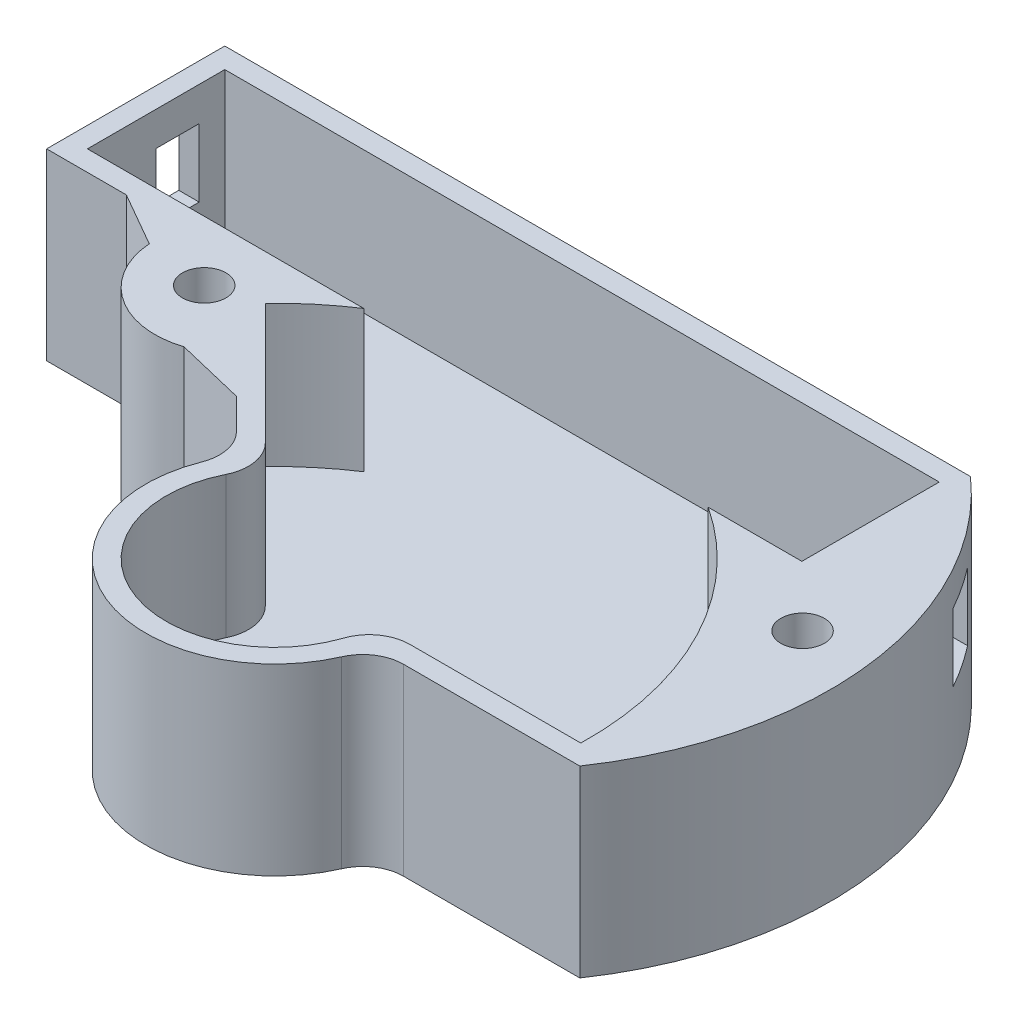
SolidWorks part; units mm, degrees
ref_plane "Alzado" through (0, 0, 0) normal (0, 0, 1) x (1, 0, 0)
ref_plane "Planta" through (0, 0, 0) normal (0, 1, 0) x (1, 0, 0)
ref_plane "Vista lateral" through (0, 0, 0) normal (1, 0, 0) x (0, 0, -1)
sketch "Croquis1" plane through (0, 0, 0) normal (0, 1, 0) x (1, 0, 0)
  line L0 (-35, 32.5) -> (35, -32.5) construction
  line L1 (-35, 32.5) -> (35, 32.5)
  line L2 (-35, 32.5) -> (-35, -32.5)
  line L3 (-35, -32.5) -> (35, -32.5)
  line L4 (35, 32.5) -> (35, -32.5)
  dimension "D1" = 70
  dimension "D2" = 65
extrude "Extruir1" add sketch "Croquis1" along normal blind 3.5
sketch "Croquis2" plane through (0, 3.5, 0) normal (0, 1, 0) x (1, 0, 0)
  line L0 (0, 32.5) -> (0, -32.5) construction
  line L1 (35, 32.5) -> (-35, 32.5) construction
  line L2 (-35, -32.5) -> (35, -32.5) construction
  circle A0 centre (0, -17.5) radius 3.1
  dimension "D1" = 6.2
  dimension "D2" = 15
extrude "Extruir2" cut sketch "Croquis2" against normal blind 5
sketch "Croquis3" plane through (0, 3.5, 0) normal (0, 1, 0) x (1, 0, 0)
  line L0 (0, -32.5) -> (0, 32.5) construction
  line L1 (-35, -32.5) -> (35, -32.5) construction
  line L2 (35, 32.5) -> (-35, 32.5) construction
  line L3 (-32.9868, -32.5) -> (-32.9868, 32.5) construction
  line L4 (-32.9868, 1.7) -> (-12.6633, 1.7)
  line L5 (18.8496, -32.5) -> (18.8496, 32.5) construction
  line L6 (-32.9868, 3.5) -> (18.8496, 3.5) construction
  line L7 (-32.9868, 2) -> (0, 2) construction
  line L8 (-32.9868, 11.5) -> (18.8496, 11.5) construction
  line L9 (0, -17.5) -> (-14.8492, -2.6508) construction
  line L10 (0, -17.5) -> (14.8492, -2.6508) construction
  line L11 (0, 2) -> (18.8496, 2) construction
  line L12 (-32.9868, 2) -> (18.8496, 2) construction
  line L13 (-32.9868, 11.8) -> (18.8496, 11.8)
  line L14 (-5.3033, -12.1967) -> (-16.2635, -1.2365) construction
  line L15 (12.6633, 1.7) -> (18.8496, 1.7)
  line L16 (-32.9868, 1.7) -> (18.8496, 1.7) construction
  line L17 (7.9844, -18) -> (22.9946, -18)
  line L18 (-5.9993, -12.2078) -> (-16.6132, -1.5939)
  line L19 (0, -17.5) -> (23, -17.5) construction
  line L20 (7.5, -17.5) -> (23, -17.5) construction
  line L21 (-5.6569, -12.5503) -> (-16.617, -1.5901) construction
  line L22 (7.5, -18) -> (23, -18) construction
  line L23 (-32.9868, 11.8) -> (-32.9868, 1.7)
  line L24 (18.8496, 11.8) -> (18.8496, 1.7)
  line L25 (-34.4868, 13.3) -> (20.3496, 13.3)
  line L26 (20.3496, 13.3) -> (20.3496, 0.2)
  line L27 (16.9399, 0.2) -> (20.3496, 0.2)
  line L28 (9.2871, -19.5) -> (24.4182, -19.5)
  line L29 (-7.9812, -12.3473) -> (-18.6805, -1.6479)
  line L30 (-34.4868, 0.2) -> (-16.9399, 0.2)
  line L31 (-34.4868, 13.3) -> (-34.4868, 0.2)
  circle A0 centre (0, -17.5) radius 21 construction
  circle A1 centre (0, -17.5) radius 7.5 construction
  arc A2 (-12.6633, 1.7) -> (-16.6132, -1.5939) centre (0, -17.5) ccw
  circle A3 centre (0, -17.5) radius 23 construction
  arc A4 (-5.9993, -12.2078) -> (7.9844, -18) centre (0, -17.5) ccw
  arc A5 (22.9946, -18) -> (12.6633, 1.7) centre (0, -17.5) ccw
  arc A6 (24.4182, -19.5) -> (16.9399, 0.2) centre (0, -17.5) ccw
  arc A7 (-7.9812, -12.3473) -> (9.2871, -19.5) centre (0, -17.5) ccw
  arc A8 (-16.9399, 0.2) -> (-18.6805, -1.6479) centre (0, -17.5) ccw
  dimension "D3" = 42
  dimension "D8" = 15
  dimension "D9" = 46
  dimension "D14" = 0.5
  dimension "D2" = 51.8364
  dimension "D6" = 90
  dimension "D7" = 45
  dimension "D1" = 32.9868
  dimension "D4" = 1.5
  dimension "D5" = 9.5
  dimension "D10" = 1.8
  dimension "D11" = 0.3
  dimension "D12" = 0.5
  dimension "D13" = 0.5
  dimension "D15" = 1.5
extrude "Extruir3" add sketch "Croquis3" along normal blind 10
sketch "Croquis4" plane through (0, 3.5, 0) normal (0, 1, 0) x (1, 0, 0)
  line L0 (-34.4868, 0.2) -> (-16.9399, 0.2) construction
  line L1 (-34.4868, 13.3) -> (-34.4868, 0.2) construction
  line L2 (20.3496, 13.3) -> (-34.4868, 13.3) construction
  line L3 (20.3496, 0.2) -> (20.3496, 13.3) construction
  line L4 (16.9399, 0.2) -> (20.3496, 0.2) construction
  line L5 (9.2871, -19.5) -> (24.4182, -19.5) construction
  line L6 (-18.6805, -1.6479) -> (-7.9812, -12.3473) construction
  line L7 (-34.4868, 0.2) -> (-16.9399, 0.2)
  line L8 (-34.4868, 13.3) -> (-34.4868, 0.2)
  line L9 (20.3496, 13.3) -> (-34.4868, 13.3)
  line L10 (20.3496, 0.2) -> (20.3496, 13.3)
  line L11 (16.9399, 0.2) -> (20.3496, 0.2)
  line L12 (9.2871, -19.5) -> (24.4182, -19.5)
  line L13 (-18.6805, -1.6479) -> (-7.9812, -12.3473)
  arc A0 (-16.9399, 0.2) -> (-18.6805, -1.6479) centre (0, -17.5) ccw construction
  arc A1 (24.4182, -19.5) -> (16.9399, 0.2) centre (0, -17.5) ccw construction
  arc A2 (-7.9812, -12.3473) -> (9.2871, -19.5) centre (0, -17.5) ccw construction
  arc A3 (-16.9399, 0.2) -> (-18.6805, -1.6479) centre (0, -17.5) ccw
  arc A4 (24.4182, -19.5) -> (16.9399, 0.2) centre (0, -17.5) ccw
  arc A5 (-7.9812, -12.3473) -> (9.2871, -19.5) centre (0, -17.5) ccw
extrude "Extruir4" cut sketch "Croquis4" against normal blind 10 flip side to cut
fillet "Redondeo1" radius 3 4 edges at (9.2871, 6.75, 19.5) (-7.9812, 6.75, 12.3473) (7.9844, 8.5, 18) (-5.9993, 8.5, 12.2078)
sketch "Croquis5" plane through (0, 0, 0) normal (0, -1, 0) x (1, 0, 0)
  line L0 (-18.6805, 1.6479) -> (-9.5151, 10.8133) construction
  line L1 (-34.4868, -0.2) -> (-16.9399, -0.2) construction
  line L2 (-18.6805, 1.6479) -> (-14.4379, 5.8906)
  line L3 (-24.3889, -0.2) -> (-16.9399, -0.2)
  line L4 (20.3496, -0.2) -> (20.3496, -13.3) construction
  line L5 (16.9399, -0.2) -> (20.3496, -0.2) construction
  line L6 (20.3496, -0.2) -> (20.3496, -13.3)
  line L7 (16.9399, -0.2) -> (20.3496, -0.2)
  arc A0 (-14.4379, 5.8906) -> (-24.3889, -0.2) centre (-18.6805, 1.6479) ccw
  arc A1 (-18.6805, 1.6479) -> (-16.9399, -0.2) centre (0, 17.5) ccw construction
  arc A2 (-18.6805, 1.6479) -> (-16.9399, -0.2) centre (0, 17.5) ccw
  arc A3 (24.4182, 19.5) -> (20.3496, -13.3) centre (3.7676, 5.4092) cw
  arc A4 (16.9399, -0.2) -> (24.4182, 19.5) centre (0, 17.5) ccw construction
  arc A5 (16.9399, -0.2) -> (24.4182, 19.5) centre (0, 17.5) ccw
  dimension "D1" = 12
  dimension "D2" = 25
extrude "Extruir5" add sketch "Croquis5" against normal up to surface (13.5 mm away) up to face at (-1.8238, 13.5, 5.5521)
chamfer "Chaflán1" distance 5 angle 45 2 edges at (-14.4379, 6.75, 5.8906) (-24.3889, 6.75, -0.2) first distance on face at (-20.613, 6.75, 4.8054) first distance on face at (-29.4378, 6.75, -0.2)
sketch "Croquis6" plane through (0, 13.5, 0) normal (0, 1, 0) x (1, 0, 0)
  line L7 (-34.4868, 13.3) -> (-34.4868, 0.2)
  line L8 (-34.4868, 0.2) -> (-28.6257, 0.2)
  line L9 (-28.6257, 0.2) -> (-24.6654, -2.0731)
  line L10 (-16.83, -7.3554) -> (-11.7523, -8.5761)
  line L11 (-11.7523, -8.5761) -> (-9.5151, -10.8133)
  line L12 (11.4564, -19.5) -> (24.4182, -19.5)
  line L13 (20.3496, 13.3) -> (-34.4868, 13.3)
  line L14 (-34.4868, 13.3) -> (-34.4868, 0.2)
  line L15 (-34.4868, 0.2) -> (-28.6257, 0.2)
  line L16 (-28.6257, 0.2) -> (-24.6654, -2.0731)
  line L17 (-16.83, -7.3554) -> (-11.7523, -8.5761)
  line L18 (-11.7523, -8.5761) -> (-9.5151, -10.8133)
  line L19 (11.4564, -19.5) -> (24.4182, -19.5)
  line L20 (20.3496, 13.3) -> (-34.4868, 13.3)
  arc A5 (-24.6654, -2.0731) -> (-16.83, -7.3554) centre (-18.6805, -1.6479) ccw
  arc A6 (-8.8437, -14.0303) -> (-9.5151, -10.8133) centre (-11.6365, -12.9346) ccw
  arc A7 (-8.8437, -14.0303) -> (8.7069, -21.3) centre (0, -17.5) ccw
  arc A8 (11.4564, -19.5) -> (8.7069, -21.3) centre (11.4564, -22.5) ccw
  arc A9 (24.4182, -19.5) -> (20.3496, 13.3) centre (3.7676, -5.4092) ccw
  arc A10 (-24.6654, -2.0731) -> (-16.83, -7.3554) centre (-18.6805, -1.6479) ccw
  arc A11 (-8.8437, -14.0303) -> (-9.5151, -10.8133) centre (-11.6365, -12.9346) ccw
  arc A12 (-8.8437, -14.0303) -> (8.7069, -21.3) centre (0, -17.5) ccw
  arc A13 (11.4564, -19.5) -> (8.7069, -21.3) centre (11.4564, -22.5) ccw
  arc A14 (24.4182, -19.5) -> (20.3496, 13.3) centre (3.7676, -5.4092) ccw
  dimension "D1" = 0
extrude "Extruir6" add sketch "Croquis6" along normal blind 3.5 separate body
sketch "Croquis7" plane through (0, 17, 0) normal (0, 1, 0) x (1, 0, 0)
  line L0 (20.3496, 13.3) -> (-34.4868, 13.3) construction
  circle A0 centre (-20, -2.7) radius 1.6
  circle A1 centre (24, -2.7) radius 1.6
  dimension "D1" = 3.2
  dimension "D2" = 16
  dimension "D3" = 20
  dimension "D4" = 24
extrude "Extruir7" cut sketch "Croquis7" against normal through all
sketch "Croquis8" plane through (0, 17, 0) normal (0, 1, 0) x (1, 0, 0)
  circle A0 centre (0, -17.5) radius 3.1 construction
  circle A1 centre (0, -17.5) radius 3.1
extrude "Extruir8" cut sketch "Croquis8" against normal blind 5
sketch "Croquis9" plane through (0, 13.5, 0) normal (0, 1, 0) x (1, 0, 0)
  line L0 (18.8496, 1.7) -> (18.8496, 11.8) construction
  line L1 (18.8496, 1.7) -> (18.8496, 11.8)
  line L2 (19.5496, 1.7) -> (19.5496, 11.8)
  line L3 (18.8496, 11.8) -> (19.5496, 11.8)
  line L4 (18.8496, 1.7) -> (19.5496, 1.7)
  dimension "D1" = 0.7
extrude "Extruir9" cut sketch "Croquis9" against normal up to surface (10 mm away) up to face at (-1.614, 3.5, 4.797)
sketch "Croquis10" plane through (19.5496, 0, 0) normal (-1, 0, 0) x (0, 0, 1)
  line L0 (-5.175, 13.5) -> (-5.175, 3.5) construction
  line L1 (-11.5, 13.5) -> (-11.5, 3.5) construction
  line L3 (-1.7, 13.5) -> (-11.8, 13.5) construction
  line L4 (-11.8, 3.5) -> (-11.8, 13.5) construction
  line L5 (-5.175, 13.5) -> (-11.5, 3.5) construction
  line L6 (-11.8, 3.5) -> (-1.7, 3.5) construction
  line L7 (-8.3375, 8.5) -> (-11.5, 13.5) construction
  line L8 (19.5, 13.5) -> (-13.3, 13.5) construction
  line L10 (-6.7562, 11) -> (-9.9187, 11)
  line L11 (-6.7562, 11) -> (-6.7562, 6)
  line L12 (-6.7562, 6) -> (-9.9187, 6)
  line L13 (-9.9187, 11) -> (-9.9187, 6)
  dimension "D1" = 6.625
  dimension "D2" = 5
  dimension "D3" = 3.1625
  dimension "D4" = 0.3
extrude "Extruir10" cut sketch "Croquis10" against normal blind 10 and the other way through all
delete or keep bodies "Sólido-Eliminar1" type delete bodies bodies 109
sketch "Croquis11" plane through (0, 3.5, 0) normal (0, 1, 0) x (1, 0, 0)
  line L7 (-32.9868, 11.8) -> (-32.9868, 1.7)
  line L8 (-32.9868, 1.7) -> (-12.6633, 1.7)
  line L9 (-16.6132, -1.5939) -> (-7.7275, -10.4796)
  line L10 (10.4283, -18) -> (22.9946, -18)
  line L11 (12.6633, 1.7) -> (19.5496, 1.7)
  line L12 (19.5496, 1.7) -> (19.5496, 11.8)
  line L13 (19.5496, 11.8) -> (-32.9868, 11.8)
  line L14 (-32.9868, 11.8) -> (-32.9868, 1.7)
  line L15 (-32.9868, 1.7) -> (-12.6633, 1.7)
  line L16 (-16.6132, -1.5939) -> (-7.7275, -10.4796)
  line L17 (10.4283, -18) -> (22.9946, -18)
  line L18 (12.6633, 1.7) -> (19.5496, 1.7)
  line L19 (19.5496, 1.7) -> (19.5496, 11.8)
  line L20 (19.5496, 11.8) -> (-32.9868, 11.8)
  arc A5 (-12.6633, 1.7) -> (-16.6132, -1.5939) centre (0, -17.5) ccw
  arc A6 (-7.1628, -13.937) -> (-7.7275, -10.4796) centre (-9.8488, -12.6009) ccw
  arc A7 (-7.1628, -13.937) -> (7.5842, -20.0455) centre (0, -17.5) ccw
  arc A8 (10.4283, -18) -> (7.5842, -20.0455) centre (10.4283, -21) ccw
  arc A9 (22.9946, -18) -> (12.6633, 1.7) centre (0, -17.5) ccw
  arc A10 (-12.6633, 1.7) -> (-16.6132, -1.5939) centre (0, -17.5) ccw
  arc A11 (-7.1628, -13.937) -> (-7.7275, -10.4796) centre (-9.8488, -12.6009) ccw
  arc A12 (-7.1628, -13.937) -> (7.5842, -20.0455) centre (0, -17.5) ccw
  arc A13 (10.4283, -18) -> (7.5842, -20.0455) centre (10.4283, -21) ccw
  arc A14 (22.9946, -18) -> (12.6633, 1.7) centre (0, -17.5) ccw
  dimension "D1" = 0
extrude "Extruir11" cut sketch "Croquis11" against normal blind 0.4
move or copy body "Sólido-Mover/Copiar1" [suppressed] bodies to move or copy 112
